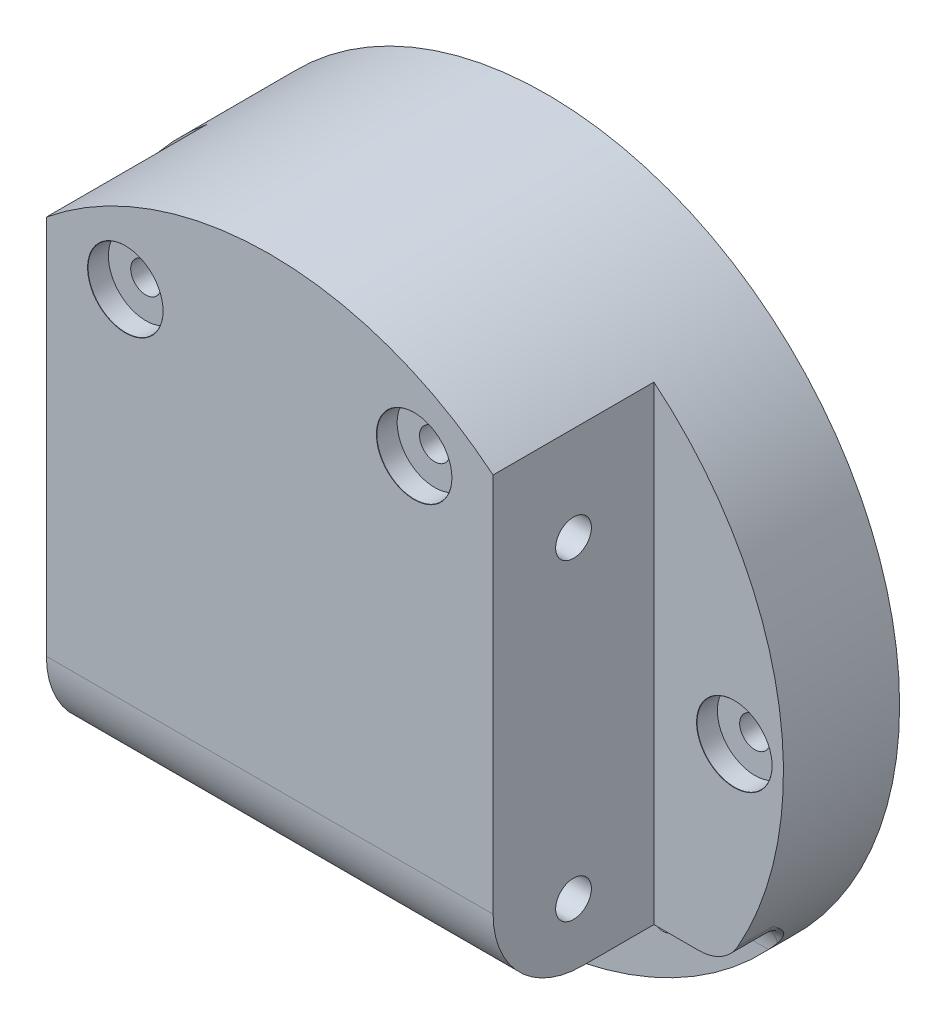
SolidWorks part; units mm, degrees
ref_plane "Plan de face" through (0, 0, 0) normal (0, 0, 1) x (1, 0, 0)
ref_plane "Plan de dessus" through (0, 0, 0) normal (0, 1, 0) x (1, 0, 0)
ref_plane "Plan de droite" through (0, 0, 0) normal (1, 0, 0) x (0, 0, -1)
sketch "Sketch1" plane through (0, 0, 0) normal (0, 0, 1) x (1, 0, 0)
  circle A0 centre (0, 0) radius 39.5
  circle A1 centre (0, 0) radius 28.5
  dimension "D1" = 79
  dimension "D2" = 57
extrude "Boss-Extrude1" add sketch "Sketch1" along normal blind 11
sketch "Sketch2" plane through (0, 0, 11) normal (0, 0, 1) x (1, 0, 0)
  circle A0 centre (0, 0) radius 39.5
extrude "Boss-Extrude2" add sketch "Sketch2" along normal blind 20
sketch "Sketch3" plane through (0, 0, 31) normal (0, 0, 1) x (1, 0, 0)
  line L0 (-32.8062, -22) -> (32.8062, -22)
  circle A0 centre (0, 0) radius 28.5
  circle A1 centre (0, 0) radius 39.5 construction
  circle A3 centre (0, 0) radius 39.5
  circle A4 centre (0, 0) radius 39.5
  circle M4 centre (0, 0) radius 39.5
  dimension "D1" = 57
  dimension "D3" = 22
  dimension "D2" = 0
extrude "Cut-Extrude3" cut sketch "Sketch3" against normal blind 27 contours A0 L0 M4 | L0 A0
sketch "Sketch4" plane through (0, 0, 31) normal (0, 0, 1) x (1, 0, 0)
  line L1 (25, -43.8944) -> (-25, -43.8944)
  line L2 (25, -43.8944) -> (25, 43.8944)
  line L3 (25, 43.8944) -> (-25, 43.8944)
  line L4 (-25, -43.8944) -> (-25, 43.8944)
  line L5 (25, -43.8944) -> (-25, 43.8944) construction
  line L6 (25, 43.8944) -> (-25, -43.8944) construction
  line L7 (-32.8062, -22) -> (32.8062, -22)
  line L8 (-32.8062, -22) -> (32.8062, -22)
  arc A1 (32.8062, -22) -> (-32.8062, -22) centre (0, 0) ccw
  arc A2 (32.8062, -22) -> (-32.8062, -22) centre (0, 0) ccw
  point P0 (0, 0)
  arc M4 (32.8062, -22) -> (-32.8062, -22) centre (0, 0) ccw
  line M5 (-32.8062, -22) -> (32.8062, -22)
  dimension "D1" = 50
  dimension "D2" = 0
extrude "Cut-Extrude4" cut sketch "Sketch4" against normal blind 18 contours L4 M5 M4 | L2 M5 M4
hole_wizard "CBORE for M3 Hex Head Machine Screw1" positions "Sketch5" profile "Sketch6" counterbore size "M3" standard "ANSI Metric"
sketch "Sketch5" plane through (0, 0, 13) normal (0, 0, 1) x (1, 0, 0)
  point P0 (-34, 0)
  point P12 (34, 0)
  point P13 (17, -29.4449)
  point P14 (-17, -29.4449)
  point P17 (0, 0)
  point P18 (-17, 29.4449)
  point P19 (0, 0)
  point P20 (17, 29.4449)
  dimension "D1" = 34
  dimension "D2" = 6
sketch "Sketch6" plane through (-34, 0, 13) normal (1, 0, 0) x (0, -1, 0)
  line L0 (0, 0) -> (0, 13)
  line L1 (0, 13) -> (1.7, 13)
  line L3 (1.7, 13) -> (1.7, 2.3)
  line L4 (4.2, 2.3) -> (1.7, 2.3)
  line L5 (4.2, 2.3) -> (4.2, 0.025)
  line L6 (4.2, 0.025) -> (4.225, 0)
  line L7 (4.225, 0) -> (0, 0)
  line L8 (-4.2, 0.025) -> (-4.225, 0) construction
  line L11 (0, -6.35) -> (0, 107.95) construction
  dimension "Thru Hole Dia." = 3.4
  dimension "Thru Hole Depth" = 13
  dimension "C'Bore Dia." = 8.4
  dimension "C'Bore Depth" = 2.3
  dimension "Near C'Sink Dia." = 8.45
  dimension "Near C'Sink Angle" = 90
fillet "Fillet2" radius 2 2 edges at (-18.1177, -22, 7.5) (18.1177, -22, 7.5)
hole_wizard "CBORE for M3 Hex Head Machine Screw2" positions "Sketch7" profile "Sketch8" counterbore size "M3" standard "ANSI Metric" end condition through all
sketch "Sketch7" plane through (0, 0, 31) normal (0, 0, 1) x (1, 0, 0)
  line L0 (0, 0) -> (0, 39.5) construction
  line L2 (0, 0) -> (-16.163, 27.9952) construction
  arc A0 (25, 30.5819) -> (-25, 30.5819) centre (0, 0) ccw construction
  point P0 (-16.163, 27.9952)
  point P16 (0, 0)
  point P17 (16.163, 27.9952)
  dimension "D1" = 30
sketch "Sketch8" plane through (-16.163, 27.9952, 31) normal (1, 0, 0) x (0, -1, 0)
  line L0 (0, 0) -> (0, 31)
  line L1 (0, 31) -> (1.7, 31)
  line L3 (1.7, 31) -> (1.7, 2.3)
  line L4 (4.2, 2.3) -> (1.7, 2.3)
  line L5 (4.2, 2.3) -> (4.2, 0.025)
  line L6 (4.2, 0.025) -> (4.225, 0)
  line L7 (4.225, 0) -> (0, 0)
  line L8 (-4.2, 0.025) -> (-4.225, 0) construction
  line L11 (0, -6.35) -> (0, 107.95) construction
  dimension "Thru Hole Dia." = 3.4
  dimension "Thru Hole Depth" = 31
  dimension "C'Bore Dia." = 8.4
  dimension "C'Bore Depth" = 2.3
  dimension "Near C'Sink Dia." = 8.45
  dimension "Near C'Sink Angle" = 90
sketch "Sketch10" plane through (-25, 0, 0) normal (-1, 0, 0) x (0, 0, 1)
  line L0 (22, 30.5819) -> (22, -22) construction
  line L1 (13, 30.5819) -> (31, 30.5819) construction
  line L2 (13, -22) -> (31, -22) construction
  circle A0 centre (22, 20) radius 2
  circle A1 centre (22, -15) radius 2
  point P10 (22, -8.817)
  point P11 (22, 20.9514)
  dimension "D1" = 4
  dimension "D2" = 15
  dimension "D3" = 20
extrude "Cut-Extrude5" cut sketch "Sketch10" against normal through all both and the other way through all
fillet "Fillet5" radius 5 2 edges at (32.8062, -22, 8.5) (-32.8062, -22, 8.5)
fillet "Fillet4" radius 5 6 edges at (21.2074, -20.8298, 4) (-21.2074, -20.8298, 4) (26.524, -22, 4) (-26.524, -22, 4) (32.5389, -21.3197, 4) (-32.5389, -21.3197, 4)
fillet "Fillet6" radius 1 3 edges at (21.2074, -20.8298, 11) (-21.2074, -20.8298, 11) (0, 28.5, 11)
fillet "Fillet7" radius 10 1 edges at (0, -22, 31)
